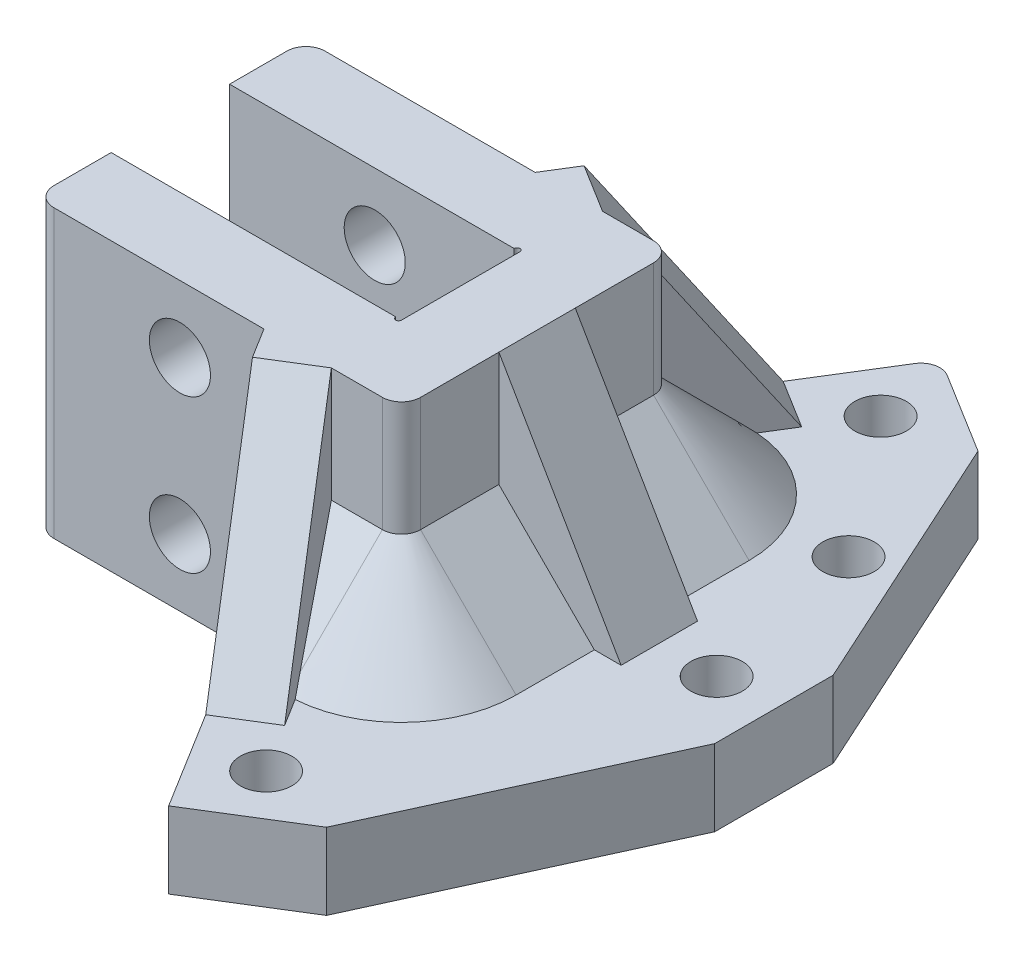
SolidWorks part; units mm, degrees
material "PLA"
ref_plane "前视基准面" through (0, 0, 0) normal (0, 0, 1) x (1, 0, 0)
ref_plane "上视基准面" through (0, 0, 0) normal (0, 1, 0) x (1, 0, 0)
ref_plane "右视基准面" through (0, 0, 0) normal (1, 0, 0) x (0, 0, -1)
sketch "草图1" plane through (0, 0, 0) normal (0, 1, 0) x (1, 0, 0)
  line L0 (-13.4985, 16.0869) -> (-15.0788, 18.637) construction
  line L1 (7.6, -3.1) -> (-7.6, -3.1) construction
  line L2 (7.6, -3.1) -> (7.6, 3.1)
  line L3 (7.6, 3.1) -> (-7.6, 3.1)
  line L4 (-7.6, -3.1) -> (-7.6, 3.1)
  line L5 (7.6, -3.1) -> (-7.6, 3.1) construction
  line L6 (7.6, 3.1) -> (-7.6, -3.1) construction
  line L7 (0, 0) -> (0, 11.678) construction
  line L8 (-4.3999, 7.1) -> (-12.5288, 20.2173)
  line L9 (-12.5288, 20.2173) -> (-17.6289, 17.0567)
  line L10 (-17.6289, 17.0567) -> (-11.6, 7.3281)
  line L11 (-11.6, 7.3281) -> (-11.6, 3.1)
  line L12 (-11.6, 3.1) -> (-24, 3.1)
  line L13 (-24, 3.1) -> (-24, -3.1)
  line L19 (-21, 0) -> (-8.6, 0) construction
  line L22 (4.3999, 7.1) -> (12.5288, 20.2173)
  line L23 (12.5288, 20.2173) -> (17.6289, 17.0567)
  line L24 (17.6289, 17.0567) -> (11.6, 7.3281)
  line L25 (11.6, 7.3281) -> (11.6, 3.1)
  line L26 (11.6, 3.1) -> (24, 3.1)
  line L30 (24, 3.1) -> (24, -3.1)
  line L31 (-4.3999, 7.1) -> (4.3999, 7.1)
  line L34 (-24, -3.1) -> (-7.6, -3.1)
  line L35 (24, -3.1) -> (7.6, -3.1)
  line L36 (0, 0) -> (-13.4985, 16.0869) construction
  circle A0 centre (0, 0) radius 21 construction
  circle A1 centre (-21, 0) radius 1.35
  circle A2 centre (-13.4985, 16.0869) radius 1.35
  circle A4 centre (13.4985, 16.0869) radius 1.35
  circle A5 centre (21, 0) radius 1.35
  dimension "D1" = 42
  dimension "D4" = 2.7
  dimension "D2" = 15.2
  dimension "D3" = 6.2
  dimension "D5" = 50
  dimension "D7" = 6
  dimension "D8" = 3
  dimension "D9" = 3
  dimension "D13" = 4
  dimension "D15" = 4
extrude "凸台-拉伸1" add sketch "草图1" along normal blind 4
sketch "草图3" plane through (0, 4, 0) normal (0, 1, 0) x (1, 0, 0)
  line L0 (0, 0) -> (0, 13.1344) construction
  line L2 (-4.3999, 7.1) -> (4.3999, 7.1)
  line L3 (4.3999, 7.1) -> (9.3682, 15.1172)
  line L4 (12.5288, 20.2173) -> (4.3999, 7.1) construction
  line L5 (9.3682, 15.1172) -> (11.9183, 13.5369)
  line L6 (11.9183, 13.5369) -> (7.9293, 7.1)
  line L7 (-7.6, 3.1) -> (7.6, 3.1) construction
  line L8 (-11.9183, 13.5369) -> (-7.9293, 7.1)
  line L9 (-9.3682, 15.1172) -> (-11.9183, 13.5369)
  line L10 (-4.3999, 7.1) -> (-9.3682, 15.1172)
  line L11 (-7.6, 3.1) -> (7.6, 3.1)
  line L12 (-11.6, -0.1) -> (-18, -0.1)
  line L13 (-7.6, -3.1) -> (-7.6, 3.1) construction
  line L15 (24, 0) -> (18.8885, 0) construction
  line L18 (-24, -3.1) -> (-7.6, -3.1) construction
  line L19 (-7.6, -3.1) -> (-18, -3.1)
  line L20 (-18, -3.1) -> (-18, -0.1)
  line L23 (11.6, 2) -> (18, 2)
  line L24 (18, -2) -> (18, 2)
  line L25 (-7.6, 3.1) -> (-7.6, -3.1)
  line L27 (-7.9293, 7.1) -> (-11.6, 7.1)
  line L28 (-11.6, 7.1) -> (-11.6, -0.1)
  line L29 (7.6, -2) -> (18, -2)
  line L30 (11.6, 7.1) -> (11.6, 2)
  line L31 (7.9293, 7.1) -> (11.6, 7.1)
  line L32 (7.6, 3.1) -> (7.6, -2)
  line L33 (24, -3.1) -> (24, 3.1) construction
  circle A0 centre (13.4985, 16.0869) radius 1.35 construction
  circle A1 centre (-21, 0) radius 1.35 construction
  circle A2 centre (21, 0) radius 1.35 construction
  dimension "D3" = 3
  dimension "D7" = 3
  dimension "D1" = 3
  dimension "D2" = 3
  dimension "D4" = 4
  dimension "D5" = 4
  dimension "D6" = 4
extrude "凸台-拉伸2" add sketch "草图3" along normal blind 11
sketch "草图4" plane through (0, 0, 3.1) normal (0, 0, 1) x (1, 0, 0)
  line L0 (-11.6, 15) -> (-11.6, 4) construction
  line L1 (-11.6, 15) -> (-11.6, 4) construction
  line L2 (-11.6, 15) -> (-18, 4)
  line L3 (-18, 4) -> (-18, 15)
  line L4 (-18, 15) -> (-11.6, 15)
  line L5 (0, 0) -> (0, 12.485) construction
  line L6 (-7.6, 0) -> (7.6, 0) construction
  line L7 (18, 4) -> (18, 15)
  line L8 (11.6, 15) -> (18, 4)
  line L9 (18, 15) -> (11.6, 15)
extrude "切除-拉伸1" cut sketch "草图4" against normal blind 10
sketch "草图5" plane through (0, 0, 0) normal (-0.85, 0, -0.5268) x (-0.5268, 0, 0.85)
  line L0 (-10.2119, 15) -> (-17.7846, 4)
  line L1 (-17.7846, 4) -> (-17.7846, 15)
  line L2 (-17.7846, 15) -> (-10.2119, 15)
  line L4 (-10.2119, 15) -> (-17.7846, 15) construction
  line L5 (-10.2119, 15) -> (-17.7846, 15) construction
extrude "切除-拉伸2" cut sketch "草图5" against normal blind 3
mirror "镜向2" about plane through (0, 0, 0) normal (1, 0, 0) of "切除-拉伸2"
sketch "草图6" plane through (0, 0, -7.1) normal (0, 0, -1) x (-1, 0, 0)
  line L0 (0, 0) -> (0, 13.5753) construction
  line L1 (-4.3999, 0) -> (4.3999, 0) construction
  line L2 (-4.3999, 7.5) -> (1.4774, 7.5) construction
  line L3 (-4.3999, 15) -> (-4.3999, 0) construction
  circle A0 centre (0, 11.5) radius 1.6
  circle A1 centre (0, 3.5) radius 1.6
  dimension "D2" = 3.2
  dimension "D1" = 8
extrude "切除-拉伸3" cut sketch "草图6" against normal through all
sketch "草图7" plane through (0, 15, 0) normal (0, 1, 0) x (1, 0, 0)
  line L0 (-7.6, 3.1) -> (7.6, 3.1) construction
  circle A0 centre (7.45, 3.1) radius 0.15
  circle A1 centre (-7.45, 3.1) radius 0.15 construction
  dimension "D1" = 0.3
extrude "切除-拉伸4" cut sketch "草图7" against normal through all
sketch "草图8" plane through (0, 15, 0) normal (0, 1, 0) x (1, 0, 0)
  line L0 (-7.6, 3.1) -> (-7.6, 27.2173) construction
  line L1 (-7.6, 3.1) -> (7.3, 3.1) construction
  line L2 (-7.6, 27.2173) -> (-31, 27.2173)
  line L3 (-31, 27.2173) -> (-31, -10.1)
  line L4 (-7.6, 3.1) -> (-7.6, -10.1)
  line L5 (-7.6, -10.1) -> (-31, -10.1)
  line L6 (-18, -3.1) -> (-11.6, -3.1) construction
  line L7 (-24, 3.1) -> (-24, -3.1) construction
  line L8 (-7.6, -3.1) -> (-7.6, 3.1) construction
  line L9 (-7.6, 7.1) -> (-2.6, 7.1)
  line L10 (4.3999, 7.1) -> (-4.3999, 7.1) construction
  line L11 (-2.6, 7.1) -> (-2.6, 27.2173)
  line L12 (-2.6, 27.2173) -> (-7.6, 27.2173)
  line L13 (-7.6, 7.1) -> (-7.6, 3.1)
  dimension "D1" = 5
  dimension "D2" = 7
  dimension "D3" = 7
  dimension "D4" = 7
extrude "切除-拉伸5" cut sketch "草图8" against normal through all
mirror "镜向3" about plane through (0, 0, 0) normal (0, 0, 1) of bodies 121
sketch "草图12" plane through (0, 4, 0) normal (0, 1, 0) x (1, 0, 0)
  line L0 (11.6, 7.3281) -> (17.6289, 17.0567)
  line L1 (17.6289, 17.0567) -> (24, 3.1)
  line L2 (24, 3.1) -> (11.6, 3.1)
  line L3 (11.6, 3.1) -> (11.6, 7.3281)
  line L4 (24, -3.1) -> (11.6, -3.1)
  line L5 (11.6, -3.1) -> (11.6, -7.3281)
  line L6 (11.6, -7.3281) -> (17.6289, -17.0567)
  line L7 (17.6289, -17.0567) -> (24, -3.1)
extrude "凸台-拉伸3" add sketch "草图12" against normal up to surface (4 mm away) up to face at (8.1458, 0, 0)
fillet "圆角1" radius 1 5 edges at (11.6, 9.5, -7.1) (12.5288, 2, -20.2173) (-7.6, 7.5, -7.1) (-7.6, 7.5, 7.1) (11.6, 9.5, 7.1)
chamfer "倒角1" distance 5 angle 45 6 edges at (9.2646, 4, -7.1) (11.3071, 4, -6.8071) (11.6, 4, -4.05) (9.2646, 4, 7.1) (11.3071, 4, 6.8071) (11.6, 4, 4.05)
sketch "草图13" plane through (0, 0, 0) normal (0, -1, 0) x (1, 0, 0)
  line L0 (0, 0) -> (19.0325, -8.875) construction
  line L1 (0, 0) -> (21, 0) construction
  circle A0 centre (0, 0) radius 21 construction
  circle A1 centre (19.0325, -8.875) radius 1.35
  circle A2 centre (13.4985, -16.0869) radius 1.35 construction
  dimension "D1" = 25
extrude "切除-拉伸6" cut sketch "草图13" against normal blind 10
